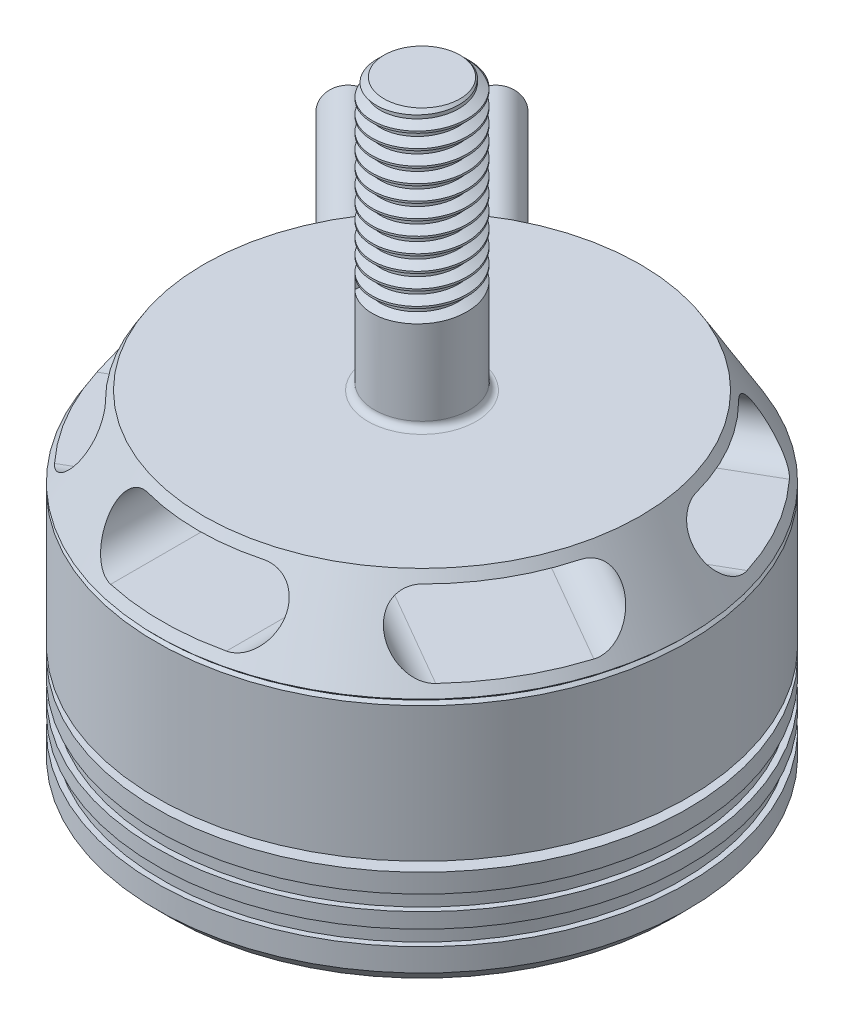
SolidWorks part; units mm, degrees
ref_plane "Front Plane" through (0, 0, 0) normal (0, 0, 1) x (1, 0, 0)
ref_plane "Top Plane" through (0, 0, 0) normal (0, 1, 0) x (1, 0, 0)
ref_plane "Right Plane" through (0, 0, 0) normal (1, 0, 0) x (0, 0, -1)
sketch "Sketch1" plane through (0, 0, 0) normal (0, 0, 1) x (1, 0, 0)
  line L0 (0, 0) -> (0, 43.4333) construction
  line L1 (0, 0) -> (-13.2, 0)
  line L2 (0, 0) -> (0, 17.5)
  line L3 (-2.85, 17.5) -> (-11.5, 17.5)
  line L4 (-14, 0.8) -> (-14, 2)
  line L5 (-11.5, 17.5) -> (-14, 13.3)
  line L6 (-2, 31.8) -> (-2.5, 31.3)
  line L7 (0, 17.5) -> (0, 31.8)
  line L8 (0, 31.8) -> (-2, 31.8)
  line L9 (-2.5, 17.85) -> (-2.5, 31.3)
  line L10 (-14, 5.9) -> (-14, 13)
  line L11 (-14, 5.9) -> (-10, 5.9)
  line L12 (-14, 13.3) -> (-13.85, 13.15)
  line L13 (-14, 5.4) -> (-10, 5.4)
  line L14 (-10, 5.9) -> (-10, 5.4)
  line L15 (-13.85, 13.15) -> (-14, 13)
  line L16 (-13.85, 13.15) -> (-14, 13.15) construction
  line L17 (-13.2, 0) -> (-14, 0.8)
  line L18 (-14, 4.4) -> (-13.7, 4.4)
  line L19 (-14, 2.8) -> (-14, 3.6)
  line L20 (-14, 3.6) -> (-13.7, 3.6)
  line L21 (-13.7, 4.4) -> (-13.7, 3.6)
  line L22 (-14, 2.8) -> (-13.7, 2.8)
  line L24 (-14, 2) -> (-13.7, 2)
  line L25 (-13.7, 2.8) -> (-13.7, 2)
  line L26 (-13.7, 2.8) -> (-13.7, 3.6) construction
  line L27 (-14, 4.4) -> (-14, 5.4)
  arc A0 (-2.85, 17.5) -> (-2.5, 17.85) centre (-2.85, 17.85) ccw
  point P1 (-14, 17.5)
  point P3 (-14, 0)
  point P5 (-2.5, 31.8)
  point P28 (-2.5, 17.5)
  dimension "D14" = 0.35
  dimension "D1" = 17.5
  dimension "D2" = 28
  dimension "D3" = 5
  dimension "D4" = 14.3
  dimension "D5" = 2.5
  dimension "D6" = 4.2
  dimension "D7" = 4
  dimension "D8" = 0.5
  dimension "D9" = 5.4
  dimension "D10" = 0.3
  dimension "D11" = 2
  dimension "D12" = 0.8
  dimension "D13" = 0.3
revolve "Revolve1" add sketch "Sketch1" angle 360 about L0
sketch "Sketch2" plane through (0, 0, 0) normal (0, -1, 0) x (1, 0, 0)
  line L0 (-13.2, 0) -> (13.2, 0) construction
  line L1 (0, 13.2) -> (0, -13.2) construction
  line L2 (0, 0) -> (-9.3338, 9.3338) construction
  line L3 (-2.5998, 8.2457) -> (0, 0) construction
  line L4 (-8.2457, 2.5998) -> (0, 0) construction
  circle A0 centre (0, 0) radius 13.2 construction
  arc A1 (-4.9841, 7.4939) -> (-7.4939, 4.9841) centre (0, 0) ccw construction
  arc A2 (-6.3686, 9.5755) -> (-9.5755, 6.3686) centre (0, 0) ccw
  arc A3 (-3.5997, 5.4123) -> (-5.4123, 3.5997) centre (0, 0) ccw
  arc A4 (-3.5997, 5.4123) -> (-6.3686, 9.5755) centre (-4.9841, 7.4939) ccw
  arc A5 (-9.5755, 6.3686) -> (-5.4123, 3.5997) centre (-7.4939, 4.9841) ccw
  circle A6 centre (0, 8) radius 1.5
  circle A7 centre (0, -8) radius 1.5
  circle A8 centre (-9.5, 0) radius 1.5
  circle A9 centre (9.5, 0) radius 1.5
  arc A10 (4.9841, 7.4939) -> (7.4939, 4.9841) centre (0, 0) cw construction
  arc A11 (6.3686, 9.5755) -> (9.5755, 6.3686) centre (0, 0) cw
  arc A12 (3.5997, 5.4123) -> (5.4123, 3.5997) centre (0, 0) cw
  arc A13 (3.5997, 5.4123) -> (6.3686, 9.5755) centre (4.9841, 7.4939) cw
  arc A14 (9.5755, 6.3686) -> (5.4123, 3.5997) centre (7.4939, 4.9841) cw
  arc A15 (-4.9841, -7.4939) -> (-7.4939, -4.9841) centre (0, 0) cw construction
  arc A16 (-6.3686, -9.5755) -> (-9.5755, -6.3686) centre (0, 0) cw
  arc A17 (-3.5997, -5.4123) -> (-5.4123, -3.5997) centre (0, 0) cw
  arc A18 (-3.5997, -5.4123) -> (-6.3686, -9.5755) centre (-4.9841, -7.4939) cw
  arc A19 (-9.5755, -6.3686) -> (-5.4123, -3.5997) centre (-7.4939, -4.9841) cw
  arc A20 (4.9841, -7.4939) -> (7.4939, -4.9841) centre (0, 0) ccw construction
  arc A21 (6.3686, -9.5755) -> (9.5755, -6.3686) centre (0, 0) ccw
  arc A22 (3.5997, -5.4123) -> (5.4123, -3.5997) centre (0, 0) ccw
  arc A23 (3.5997, -5.4123) -> (6.3686, -9.5755) centre (4.9841, -7.4939) ccw
  arc A24 (9.5755, -6.3686) -> (5.4123, -3.5997) centre (7.4939, -4.9841) ccw
  circle A25 centre (0, 0) radius 14 construction
  point P10 (-6.364, 6.364)
  point P27 (6.364, 6.364)
  point P34 (-6.364, -6.364)
  point P41 (6.364, -6.364)
  dimension "D2" = 3
  dimension "D5" = 6.5
  dimension "D6" = 2.5
  dimension "D1" = 45
  dimension "D3" = 8
  dimension "D4" = 9.5
  dimension "D7" = 55
extrude "Cut-Extrude1" cut sketch "Sketch2" against normal up to surface (5.4 mm away) up to face at (0, 5.4, -14)
ref_plane "Plane1" through (0, 0, 14) normal (0, 0, 1) x (1, 0, 0)
sketch "Sketch3" plane through (0, 0, 14) normal (0, 0, 1) x (1, 0, 0)
  line L0 (11.5, 17.5) -> (-11.5, 17.5) construction
  line L1 (11.5, 17.5) -> (-11.5, 17.5) construction
  line L2 (14, 13.3) -> (-14, 13.3) construction
  line L3 (14, 13.3) -> (-14, 13.3) construction
  line L4 (0, 17.5) -> (0, 6.3764) construction
  line L5 (-3.05, 15.4) -> (3.05, 15.4) construction
  line L6 (-3.05, 17) -> (3.05, 17)
  line L7 (-3.05, 13.8) -> (3.05, 13.8)
  line L8 (4.65, 15.4) -> (4.65, 16.6899) construction
  line L9 (-4.65, 15.4) -> (-4.65, 16.6899) construction
  arc A0 (-3.05, 17) -> (-3.05, 13.8) centre (-3.05, 15.4) ccw
  arc A1 (3.05, 13.8) -> (3.05, 17) centre (3.05, 15.4) ccw
  point P9 (0, 15.4)
  dimension "D1" = 9.3
  dimension "D2" = 3.2
  dimension "D3" = 1
extrude "Cut-Extrude2" cut sketch "Sketch3" against normal blind 9
pattern_circular "CirPattern1" count 6 over 360 about axis through (0, 0, 0) along (0, -1, 0) of "Cut-Extrude2"
sketch "Sketch4" plane through (0, 0, 0) normal (0, 0, 1) x (1, 0, 0)
  line L0 (0, 26.3855) -> (0, 3.8332) construction
  line L1 (-3.05, 13.8) -> (-10.0439, 13.8) construction
  line L2 (-3.05, 17) -> (-8.3447, 17) construction
  line L3 (-3.05, 13.8) -> (-10.0439, 13.8) construction
  line L4 (-3.05, 17) -> (-8.3447, 17) construction
  line L6 (-6, 17) -> (-4.5, 17)
  line L7 (-6, 17) -> (-6, 13.8)
  line L8 (-6, 13.8) -> (-4.5, 13.8)
  line L9 (-4.5, 17) -> (-4.5, 13.8)
  line L11 (-6.1, 17) -> (-11.3947, 17)
  line L12 (-13.0939, 13.8) -> (-6.1, 13.8)
  line L13 (-6.1, 17) -> (-11.3947, 17) construction
  line L14 (-13.0939, 13.8) -> (-6.1, 13.8) construction
  ellipse E1 centre (-6.1, 15.4) end of major axis (-9.3, 15.4) minor radius 1.6 (-6.1, 17) -> (-6.1, 13.8) ccw
  ellipse E2 centre (-6.1, 15.4) end of major axis (-9.3, 15.4) minor radius 1.6 (-6.1, 17) -> (-6.1, 13.8) ccw construction
  spline S1 degree 3 poles (-3795.7281, -1197.0465) (-182.2602, -495.817) (-1.3589, 27.0142) (-11.6833, 16.8059) (-11.7357, 16.7465) (-11.8479, 16.6064) (-11.9071, 16.5265) (-12.0273, 16.3549) (-12.0896, 16.2613) (-12.2124, 16.0701) (-12.2738, 15.971) (-12.4551, 15.6703) (-12.5701, 15.4685) (-12.7784, 15.083) (-12.8728, 14.897) (-12.9908, 14.6421) (-13.0264, 14.5609) (-13.0894, 14.4059) (-13.1168, 14.3319) (-13.1607, 14.1966) (-13.1774, 14.1347) (-13.199, 14.0233) (-13.204, 13.9733) (-13.1992, 13.8903) (-13.1897, 13.8576) (-10.9763, 11.0279) (122.3917, 168.3449) (-1024.9148, 3879.2292) knots -12.948482 -12.948482 -12.948482 -12.948482 0.125 0.125 0.1875 0.1875 0.25 0.25 0.3125 0.3125 0.375 0.375 0.5 0.5 0.625 0.625 0.6875 0.6875 0.75 0.75 0.8125 0.8125 0.875 0.875 0.9375 0.9375 8.678093 8.678093 8.678093 8.678093 only from (-11.3947, 17) to (-13.0939, 13.8)
  spline S2 degree 3 poles (-11.3947, 17) (-11.4552, 17) (-11.5359, 16.9516) (-11.6833, 16.8059) (-11.7357, 16.7465) (-11.8479, 16.6064) (-11.9071, 16.5265) (-12.0273, 16.3549) (-12.0896, 16.2613) (-12.2124, 16.0701) (-12.2738, 15.971) (-12.4551, 15.6703) (-12.5701, 15.4685) (-12.7784, 15.083) (-12.8728, 14.897) (-12.9908, 14.6421) (-13.0264, 14.5609) (-13.0894, 14.4059) (-13.1168, 14.3319) (-13.1607, 14.1966) (-13.1774, 14.1347) (-13.199, 14.0233) (-13.204, 13.9733) (-13.1992, 13.8903) (-13.1897, 13.8576) (-13.1543, 13.8122) (-13.128, 13.8) (-13.0939, 13.8) knots 0 0 0 0 0.125 0.125 0.1875 0.1875 0.25 0.25 0.3125 0.3125 0.375 0.375 0.5 0.5 0.625 0.625 0.6875 0.6875 0.75 0.75 0.8125 0.8125 0.875 0.875 0.9375 0.9375 1 1 1 1 construction
  dimension "D1" = 9
  dimension "D3" = 0.1
  dimension "D2" = 0
revolve "Cut-Revolve1" cut sketch "Sketch4" angle 360 about L0
thread "Thread2" pitch 0.8 method cut profile "Thread Profile2" start angle 0, offset 1, length 9.5, pitch 0.8, diameter 5
ref_plane "Plane3" through (-2.5, 32.3, 0) normal (0, 0, 1) x (-1, 0, 0)
sketch "Thread Profile2" plane through (-2.5, 32.3, 0) normal (0, 0, 1) x (-1, 0, 0)
  line L0 (0, 0) -> (0, 0.8) construction
  line L11 (0, 0) -> (0, 0.7)
  line L12 (0, 0.7) -> (-0.433, 0.45)
  line L13 (-0.433, 0.45) -> (-0.433, 0.25)
  line L15 (-0.433, 0.25) -> (0, 0)
  line L17 (-0.433, 0.35) -> (0, 0.35) construction
  point P2 (0, 0)
  dimension "Pitch" = 0.8
  dimension "Profile_Angle" = 60
  dimension "Profile_Land" = 0.2
  dimension "Profile_Height" = 0.433
ref_plane "Plane6" through (-9.8995, 0, -9.8995) normal (-0.7071, 0, -0.7071) x (0, -1, 0)
sketch "Sketch16" plane through (-9.8995, 0, -9.8995) normal (-0.7071, 0, -0.7071) x (0, -1, 0)
  line L0 (0, 0) -> (-32.5465, 0) construction
  line L1 (-2.65, -2.75) -> (-2.65, 2.75) construction
  line L2 (-4.4, -2.75) -> (-4.4, 2.75)
  line L3 (-0.9, -2.75) -> (-0.9, 2.75)
  line L4 (-4.4, -14) -> (-4.4, 14) construction
  line L5 (-4.4, -14) -> (-4.4, 14) construction
  line L6 (-2.65, 4.5) -> (-1.384, 4.5) construction
  line L7 (-2.65, -4.5) -> (-1.384, -4.5) construction
  arc A0 (-4.4, -2.75) -> (-0.9, -2.75) centre (-2.65, -2.75) ccw
  arc A1 (-0.9, 2.75) -> (-4.4, 2.75) centre (-2.65, 2.75) ccw
  point P5 (-2.65, 0)
  dimension "D1" = 3.5
  dimension "D2" = 9
extrude "Cut-Extrude3" cut sketch "Sketch16" against normal blind 7
sketch "Sketch17" plane through (-9.8995, 0, -9.8995) normal (-0.7071, 0, -0.7071) x (0, -1, 0)
  line L0 (-2.65, 2.75) -> (-2.65, -2.75) construction
  line L1 (-1.1, 2.75) -> (-1.1, -2.75)
  line L2 (-4.2, 2.75) -> (-4.2, -2.75)
  line L5 (-4.4, 2.75) -> (-4.4, -2.75)
  line L6 (-0.9, -2.75) -> (-0.9, 2.75)
  line L7 (-4.4, 2.75) -> (-4.4, -2.75) construction
  line L8 (-0.9, -2.75) -> (-0.9, 2.75) construction
  arc A0 (-1.1, 2.75) -> (-4.2, 2.75) centre (-2.65, 2.75) ccw
  arc A1 (-4.2, -2.75) -> (-1.1, -2.75) centre (-2.65, -2.75) ccw
  arc A4 (-0.9, 2.75) -> (-4.4, 2.75) centre (-2.65, 2.75) ccw
  arc A5 (-4.4, -2.75) -> (-0.9, -2.75) centre (-2.65, -2.75) ccw
  arc A6 (-0.9, 2.75) -> (-4.4, 2.75) centre (-2.65, 2.75) ccw construction
  arc A7 (-4.4, -2.75) -> (-0.9, -2.75) centre (-2.65, -2.75) ccw construction
  point P2 (-2.65, 0)
  dimension "D2" = 0.2
  dimension "D1" = 0
extrude "Boss-Extrude1" add sketch "Sketch17" against normal blind 5 separate body
sketch "Sketch18" plane through (-9.8995, 0, -9.8995) normal (-0.7071, 0, -0.7071) x (-0.7071, 0, 0.7071)
  line L2 (2.75, 4.2) -> (-2.75, 4.2)
  line L3 (-2.75, 1.1) -> (2.75, 1.1)
  line L4 (2.75, 4.2) -> (-2.75, 4.2)
  line L5 (-2.75, 1.1) -> (2.75, 1.1)
  arc A2 (2.75, 1.1) -> (2.75, 4.2) centre (2.75, 2.65) ccw
  arc A3 (-2.75, 4.2) -> (-2.75, 1.1) centre (-2.75, 2.65) ccw
  arc A4 (2.75, 1.1) -> (2.75, 4.2) centre (2.75, 2.65) ccw
  arc A5 (-2.75, 4.2) -> (-2.75, 1.1) centre (-2.75, 2.65) ccw
  dimension "D1" = 0
extrude "Boss-Extrude2" add sketch "Sketch18" along normal blind 5 draft 4
sketch "Sketch19" plane through (-13.435, 0, -13.435) normal (-0.7071, 0, -0.7071) x (-0.7071, 0, 0.7071)
  line L0 (-2.75, 2.65) -> (2.75, 2.65) construction
  line L2 (2.75, 3.8504) -> (-2.75, 3.8504)
  line L3 (-2.75, 1.4496) -> (2.75, 1.4496)
  line L4 (2.75, 3.8504) -> (-2.75, 3.8504) construction
  line L5 (-2.75, 1.4496) -> (2.75, 1.4496) construction
  circle A0 centre (-2.75, 2.65) radius 1.2004
  circle A1 centre (2.75, 2.65) radius 1.2004
  arc A2 (2.75, 1.4496) -> (2.75, 3.8504) centre (2.75, 2.65) ccw
  arc A3 (-2.75, 3.8504) -> (-2.75, 1.4496) centre (-2.75, 2.65) ccw
  arc A4 (2.75, 1.4496) -> (2.75, 3.8504) centre (2.75, 2.65) ccw construction
  arc A5 (-2.75, 3.8504) -> (-2.75, 1.4496) centre (-2.75, 2.65) ccw construction
  circle A6 centre (0, 2.65) radius 1.2004
  dimension "D1" = 0
extrude "Boss-Extrude3" add sketch "Sketch19" along normal blind 20
sketch "Sketch20" plane through (0, 0, 0) normal (0, -1, 0) x (1, 0, 0)
  circle A0 centre (0, 0) radius 4.6
  dimension "D1" = 9.2
extrude "Cut-Extrude4" cut sketch "Sketch20" against normal blind 2.5 draft 20
fillet "Fillet1" radius 1 4 edges at (-3.3234, 2.65, -9.4045) (-6.364, 4.2, -6.364) (-9.4045, 2.65, -3.3234) (-6.364, 1.1, -6.364)
